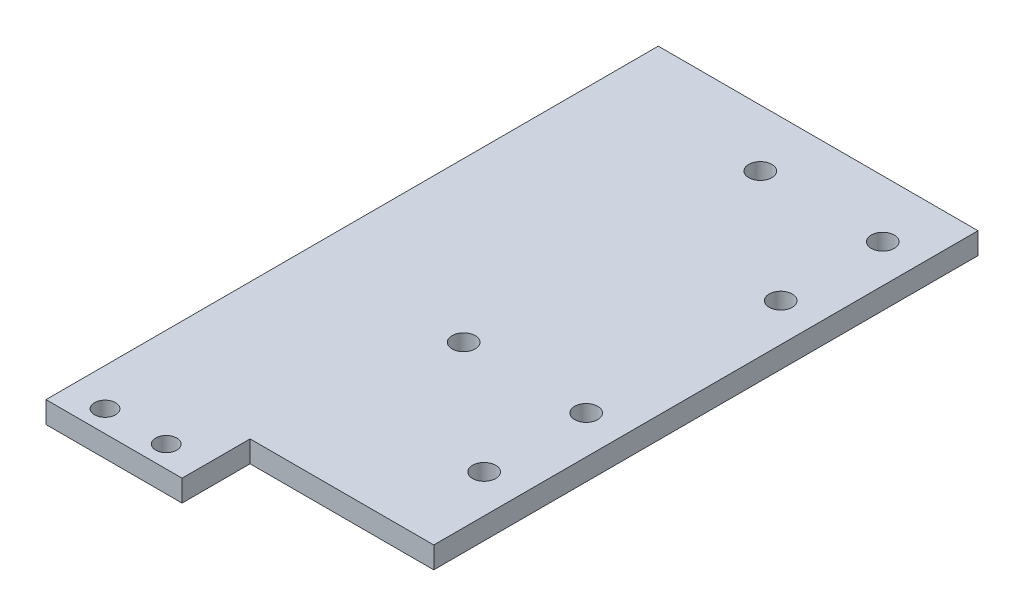
SolidWorks part; units mm, degrees
material "6061 Alloy"
ref_plane "Front Plane" through (0, 0, 0) normal (0, 0, 1) x (1, 0, 0)
ref_plane "Top Plane" through (0, 0, 0) normal (0, 1, 0) x (1, 0, 0)
ref_plane "Right Plane" through (0, 0, 0) normal (1, 0, 0) x (0, 0, -1)
sketch "Sketch1" plane through (0, 0, 0) normal (0, 1, 0) x (1, 0, 0)
  line L0 (0, 0) -> (0, 90)
  line L1 (0, 90) -> (47, 90)
  line L2 (47, 90) -> (47, 10)
  line L3 (47, 10) -> (20, 10)
  line L4 (20, 10) -> (20, 0)
  line L5 (0, 0) -> (20, 0)
  line L16 (20, 0) -> (20, 6.35) construction
  line L17 (14.5, 3.175) -> (5.5, 3.175) construction
  circle A5 centre (41.4, 81.6) radius 1.7
  circle A6 centre (14.5, 3.175) radius 1.55
  circle A7 centre (23.4, 81.6) radius 1.7
  circle A9 centre (5.5, 3.175) radius 1.55
  circle A12 centre (41.4, 23) radius 1.7 construction
  circle A13 centre (41.4, 38) radius 1.7 construction
  circle A14 centre (23.4, 38) radius 1.7 construction
  circle A15 centre (41.4, 23) radius 1.7
  circle A16 centre (41.4, 38) radius 1.7
  circle A17 centre (23.4, 38) radius 1.7
  circle A18 centre (41.4, 66.6) radius 1.7
  point P20 (10, 3.175)
  point P21 (10, 0)
  dimension "D2" = 3.1
  dimension "D3" = 3.1
  dimension "D1" = 80
  dimension "D9" = 47
  dimension "D11" = 10
  dimension "D4" = 9
  dimension "D5" = 3.175
  dimension "D6" = 15
  dimension "D7" = 8.4
extrude "Boss-Extrude1" add sketch "Sketch1" along normal blind 3.175
equation "\"D3@Sketch1\"=\"D2@Sketch1\""
